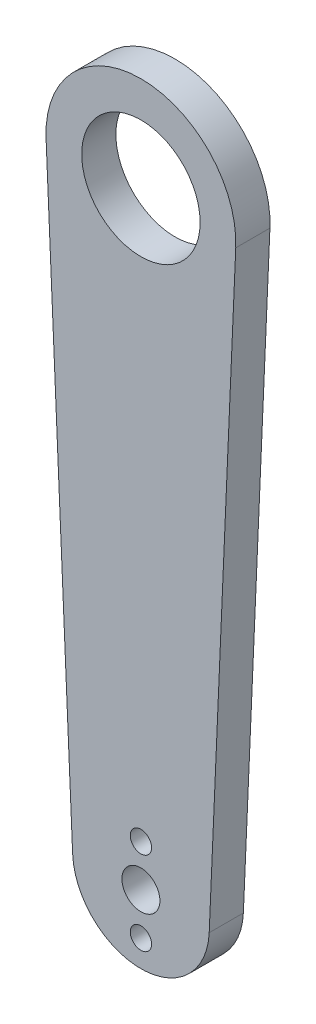
SolidWorks part; units mm, degrees
ref_plane "Front Plane" through (0, 0, 0) normal (0, 0, 1) x (1, 0, 0)
ref_plane "Top Plane" through (0, 0, 0) normal (0, 1, 0) x (1, 0, 0)
ref_plane "Right Plane" through (0, 0, 0) normal (1, 0, 0) x (0, 0, -1)
ref_axis "X Axis" through (-88.99, 0, 0) along (1, 0, 0)
ref_axis "Y Axiz" through (0, 0, 55) along (0, 0, -1)
ref_axis "Z Axis" through (0, 55, 0) along (0, -1, 0)
sketch "Sketch1" plane through (0, 0, 0) normal (0, 0, 1) x (1, 0, 0)
  line L1 (-8.9914, -0.3938) -> (-12.488, 79.4531)
  line L3 (0, -5.5) -> (0, 5.5) construction
  line L4 (12.488, 79.4531) -> (8.9914, -0.3938)
  line L5 (0, 0) -> (0, 80) construction
  arc A1 (-8.9914, -0.3938) -> (8.9914, -0.3938) centre (0, 0) ccw
  circle A2 centre (0, 80) radius 7.8
  arc A3 (12.488, 79.4531) -> (-12.488, 79.4531) centre (0, 80) ccw
  circle A5 centre (0, 0) radius 2.5
  circle A6 centre (0, 5.5) radius 1.4
  circle A7 centre (0, -5.5) radius 1.4
  point P7 (0, 0)
  dimension "D1" = 5
  dimension "D3" = 18
  dimension "D4" = 15.6
  dimension "D5" = 25
  dimension "D2" = 2.8
  dimension "D6" = 80
  dimension "D7" = 5.5
extrude "Boss-Extrude1" add sketch "Sketch1" along normal blind 4.5
